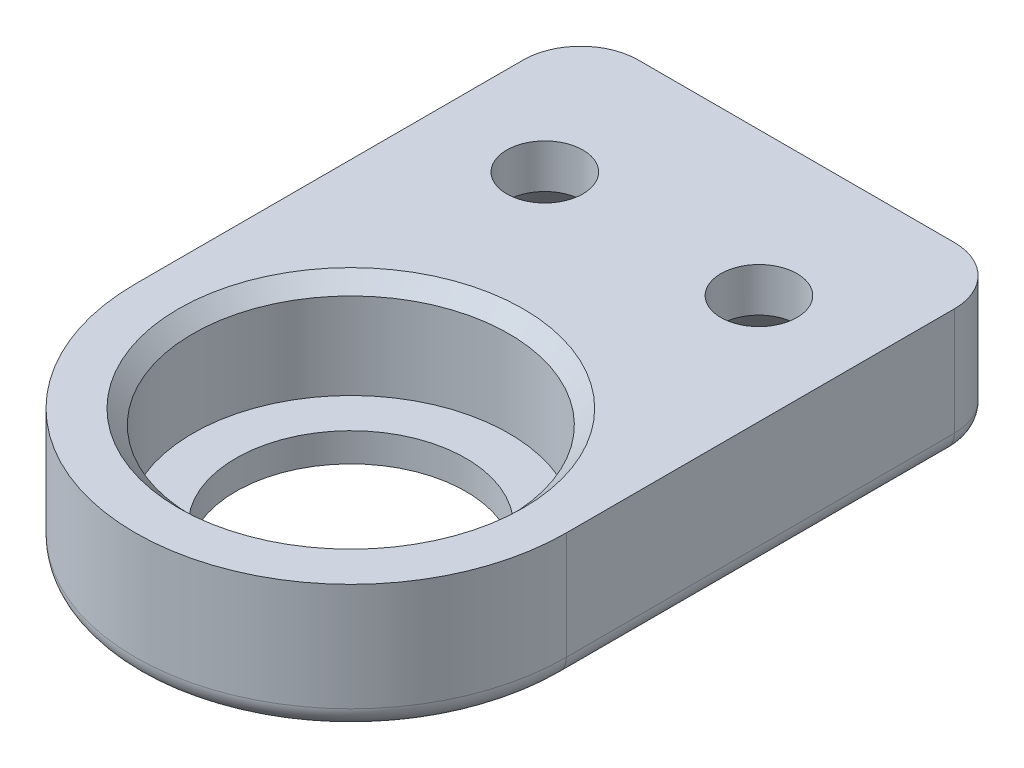
SolidWorks part; units mm, degrees
ref_plane "Front Plane" through (0, 0, 0) normal (0, 0, 1) x (1, 0, 0)
ref_plane "Top Plane" through (0, 0, 0) normal (0, 1, 0) x (1, 0, 0)
ref_plane "Right Plane" through (0, 0, 0) normal (1, 0, 0) x (0, 0, -1)
sketch "Sketch2" plane through (0, 0, 0) normal (0, 1, 0) x (1, 0, 0)
  line L1 (-15, 0) -> (15, 0)
  line L2 (-15, 0) -> (-15, 31)
  line L3 (-15, 31) -> (15, 31)
  line L4 (15, 0) -> (15, 31)
  circle A0 centre (0, 0) radius 11
  arc A1 (15, 0) -> (-15, 0) centre (0, 0) cw
  circle A2 centre (0, 0) radius 8
  point P8 (11, 0)
  point P9 (-11, 0)
  point P11 (0, 11)
  dimension "D1" = 22
  dimension "16" = 16
  dimension "D4" = 31
  dimension "30" = 30
extrude "Boss-Extrude1" add sketch "Sketch2" along normal blind 9 contours A1 L1 A0 | A0 L1 L4 L3 L2 region at (0, 0, -18.2823) region at (13, 0, 0.3354)
extrude "Boss-Extrude2" add sketch "Sketch2<3>" along normal blind 2 contours A2 L1 A0 | A2 L1 A0 region at (0, 0, -8.246) region at (9.5, 0, 0.246)
sketch "Sketch2<3>" plane through (0, 0, 0) normal (0, 1, 0) x (1, 0, 0) same geometry as "Sketch2"
hole_wizard "CBORE for M5 SBHCS1" positions "3DSketch2" profile "Sketch3" counterbore size "M5" standard "ANSI Metric" end condition through all
sketch3d "3DSketch2"
  line L0 (15, 0, 0) -> (15, 0, -31) construction
  line L1 (-15, 0, -31) -> (15, 0, -31) construction
  line L2 (-15, 0, 0) -> (-15, 0, -31) construction
  point P0 (7.4, 0, -21)
  point P2 (-7.5, 0, -21)
  dimension "D1" = 7.6
  dimension "D2" = 10
  dimension "D3" = 10
  dimension "D4" = 7.5
sketch "Sketch3" plane through (7.4, 0, -21) normal (1, 0, 0) x (0, 0, -1)
  line L0 (0, 0) -> (0, 9)
  line L1 (0, 9) -> (2.65, 9)
  line L3 (2.65, 9) -> (2.65, 2.75)
  line L4 (2.65, 2.75) -> (5.25, 2.75)
  line L5 (5.25, 2.75) -> (5.25, 0)
  line L7 (5.25, 0) -> (0, 0)
  line L11 (0, -6.35) -> (0, 107.95) construction
  dimension "Thru Hole Dia." = 5.3
  dimension "Thru Hole Depth" = 9
  dimension "C'Bore Dia." = 10.5
  dimension "C'Bore Depth" = 2.75
fillet "Fillet1" radius 4 2 edges at (-15, 4.5, -31) (15, 4.5, -31)
fillet "Fillet2" radius 1.5 6 edges at (0, 0, 15) (-15, 0, -13.5) (-13.8284, 0, -29.8284) (0, 0, -31) (13.8284, 0, -29.8284) (15, 0, -13.5)
chamfer "Chamfer1" distance 1 angle 45 1 edges at (0, 9, 11)
chamfer "Chamfer2" distance 3.2 angle 45 2 edges at (7.4, 2.75, -23.65) (-7.5, 2.75, -23.65)
